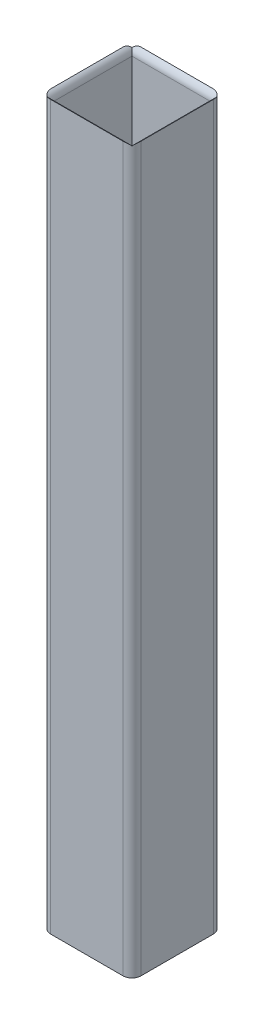
SolidWorks part; units mm, degrees
ref_plane "Front Plane" through (0, 0, 0) normal (0, 0, 1) x (1, 0, 0)
ref_plane "Top Plane" through (0, 0, 0) normal (0, 1, 0) x (1, 0, 0)
ref_plane "Right Plane" through (0, 0, 0) normal (1, 0, 0) x (0, 0, -1)
sketch "Sketch1" plane through (0, 0, 0) normal (0, 0, 1) x (1, 0, 0)
  line L1 (0, 0) -> (50, 0)
  line L2 (0, 0) -> (0, 400)
  line L3 (0, 400) -> (50, 400)
  line L4 (50, 0) -> (50, 400)
  dimension "D1" = 400
  dimension "D2" = 50
extrude "Boss-Extrude1" add sketch "Sketch1" along normal blind 50
sketch "Sketch2" plane through (0, 400, 0) normal (0, 1, 0) x (1, 0, 0)
  line L0 (50, 0) -> (0, 0) construction
  line L1 (2.5, -2.5) -> (47.5, -2.5)
  line L2 (2.5, -2.5) -> (2.5, -47.5)
  line L3 (2.5, -47.5) -> (47.5, -47.5)
  line L4 (47.5, -2.5) -> (47.5, -47.5)
  line L5 (50, -50) -> (50, 0) construction
  line L6 (50, -50) -> (0, -50) construction
  line L7 (0, -50) -> (0, 0) construction
  dimension "D1" = 2.5
  dimension "D2" = 2.5
  dimension "D3" = 2.5
  dimension "D4" = 2.5
extrude "Cut-Extrude1" cut sketch "Sketch2" against normal through all
fillet "Fillet1" radius 5 4 edges at (50, 200, 50) (50, 200, 0) (0, 200, 50) (0, 200, 0)
fillet "Fillet2" radius 5 4 edges at (47.5, 400, 25) (25, 400, 47.5) (2.5, 400, 25) (25, 400, 2.5)
